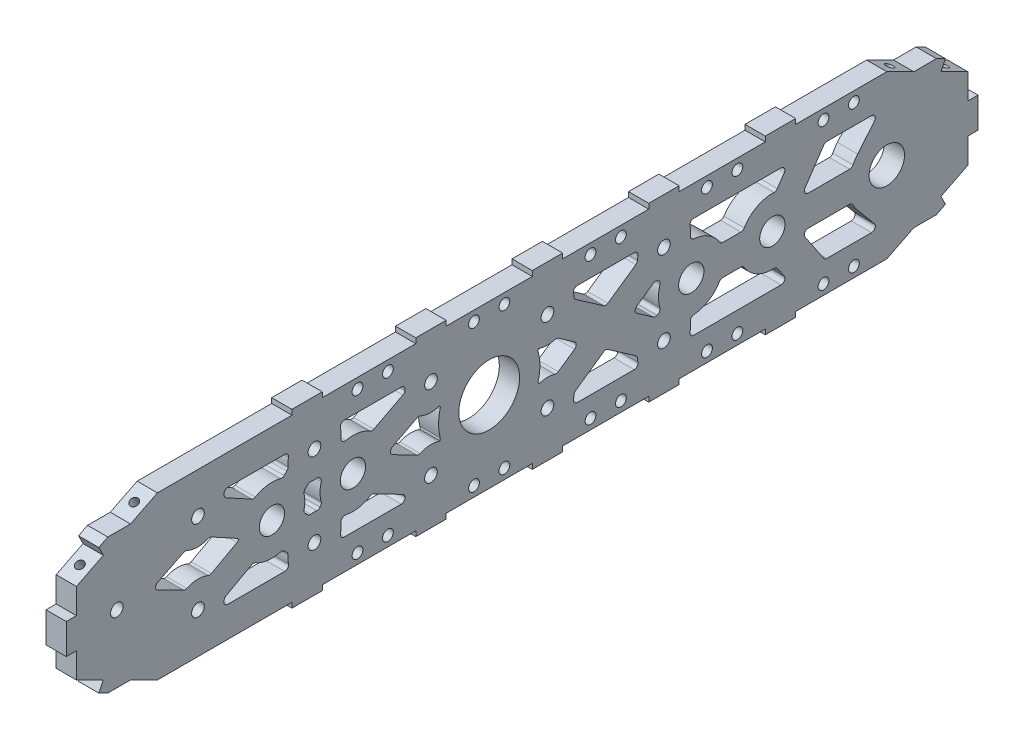
SolidWorks part; units mm, degrees
material "6061-T6 (SS)"
ref_plane "Front Plane" through (0, 0, 0) normal (0, 0, 1) x (1, 0, 0)
ref_plane "Top Plane" through (0, 0, 0) normal (0, 1, 0) x (1, 0, 0)
ref_plane "Right Plane" through (0, 0, 0) normal (1, 0, 0) x (0, 0, -1)
sketch "Sketch1" plane through (0, 0, 0) normal (1, 0, 0) x (0, 0, -1)
  line L0 (-160.655, 50.8) -> (93.345, 50.8)
  line L1 (93.345, 50.8) -> (93.345, -50.8)
  line L2 (93.345, -50.8) -> (-160.655, -50.8)
  line L3 (93.345, 0) -> (55.245, 50.8)
  line L4 (93.345, 0) -> (55.245, -50.8)
  circle A0 centre (0, 0) radius 38.1
  circle A1 centre (0, 0) radius 7.9375
  circle A2 centre (-38.1, 0) radius 7.9375
  circle A3 centre (-88.9, 0) radius 7.9375
  circle A4 centre (-88.9, 0) radius 39.751
  circle A5 centre (-38.1, 0) radius 25.4
  circle A6 centre (-160.655, 0) radius 11.1125
  circle A7 centre (-88.9, 0) radius 23.368
  circle A8 centre (-160.655, 0) radius 33.655
  circle A9 centre (-160.655, 0) radius 76.2
  circle A10 centre (-160.655, 0) radius 50.8
  dimension "D1" = 38.1
  dimension "D3" = 71.755
  dimension "D4" = 15.875
  dimension "D5" = 101.6
  dimension "D9" = 50.8
  dimension "D10" = 67.31
  dimension "D11" = 79.502
  dimension "D12" = 46.736
  dimension "D2" = 50.8
  dimension "D6" = 254
  dimension "D7" = 38.1
  dimension "D8" = 38.1
extrude "Boss-Extrude1" add sketch "Sketch1" along normal blind 12.7 contours A5 A0 A1 | A0 A5 | A10 A7 A9 A3 | A10 A7 A9 A4 | A7 A10 A4 | A7 A10 | A10 A4 A9 A7 | A9 A4 A5 A7 | A10 L2 A9 A4 | A4 A10 A8 | A8 A6 | A10 A4 A9 L0 | A9 A4 A5 A0 L2 L4 L3 L0 | A9 A3 A7 | A4 A5 | A0 A5 A4 A2 | A4 A8 | A6 | A1 region at (0, 24.069, -72.5203) region at (0, 42.9334, 118.4345) region at (0, 43.3242, 136.8815) region at (0, 26.7507, 103.5231) region at (0, 35.0406, 72.108) region at (0, -42.9334, 118.4345) region at (0, 0, 119.1262) region at (0, 24.4524, 42.4444) region at (0, 0, 55.9937) region at (0, 0, 97.9886) region at (0, 0, 76.9553) region at (0, -26.7507, 103.5231) region at (0, 0, 127.8393) region at (0, 0, 129.5966) region at (0, 0, 110.9718) region at (0, 0, 24.8917) region at (0, 34.9598, -12.3602) region at (0, 0, 0) region at (0, 0, 160.655)
hole_wizard "3/8-16 Tapped Hole1" positions "Sketch8" profile "Sketch7" tap size "3/8-16" standard "ANSI Inch"
sketch "Sketch8" plane through (12.7, 0, 0) normal (1, 0, 0) x (0, 0, -1)
  line L0 (10.795, 25.4) -> (-62.23, 25.4) construction
  line L1 (-62.23, 25.4) -> (-135.255, 25.4) construction
  line L2 (-135.255, 25.4) -> (-135.255, -25.4) construction
  line L3 (-135.255, -25.4) -> (-62.23, -25.4) construction
  line L4 (-62.23, -25.4) -> (10.795, -25.4) construction
  line L5 (10.795, -25.4) -> (10.795, 25.4) construction
  line L7 (-62.23, 25.4) -> (-62.23, -25.4) construction
  line L9 (93.345, 0) -> (61.595, 0) construction
  line L10 (61.595, 0) -> (-186.055, 0) construction
  line L11 (-186.055, 0) -> (-211.455, 0) construction
  line L16 (-160.655, 50.8) -> (55.245, 50.8) construction
  line L17 (55.245, -50.8) -> (-160.655, -50.8) construction
  arc A0 (-160.655, 50.8) -> (-160.655, -50.8) centre (-160.655, 0) ccw construction
  circle A1 centre (61.595, 0) radius 25.4
  circle A2 centre (10.795, 25.4) radius 25.4
  circle A3 centre (-62.23, 25.4) radius 25.4
  circle A4 centre (-135.255, 25.4) radius 25.4
  circle A5 centre (-186.055, 0) radius 25.4
  point P0 (61.595, 0)
  point P6 (-62.23, -25.4)
  point P8 (-135.255, -25.4)
  point P10 (-62.23, 25.4)
  point P12 (-135.255, 25.4)
  point P14 (-186.055, 0)
  dimension "D5" = 50.8
  dimension "D1" = 25.4
  dimension "D2" = 31.75
  dimension "D3" = 25.4
  dimension "D4" = 25.4
  dimension "D6" = 50.8
sketch "Sketch7" plane through (12.7, 0, -61.595) normal (0, 1, 0) x (0, 0, -1)
  line L0 (0, 0) -> (0, 26.2607)
  line L1 (0, 26.2607) -> (3.9687, 23.876)
  line L2 (3.9687, 23.876) -> (3.9687, 0)
  line L5 (3.9687, 0) -> (0, 0)
  line L10 (0, 26.2607) -> (-3.9688, 23.876) construction
  line L11 (0, -6.35) -> (0, 107.95) construction
  dimension "Tap Drill Dia." = 7.9375
  dimension "Tap Drill Depth" = 23.876
  dimension "Drill Angle" = 118
sketch "Sketch10" plane through (12.7, 0, 0) normal (1, 0, 0) x (0, 0, -1)
  line L0 (-211.455, 25.4) -> (-160.655, 50.8)
  line L1 (-211.455, 25.4) -> (-160.655, 50.8) construction
  line L2 (-160.655, 50.8) -> (-211.455, 50.8)
  line L3 (-211.455, 50.8) -> (-211.455, 25.4)
  line L4 (-211.455, -25.4) -> (-160.655, -50.8)
  line L5 (-160.655, -50.8) -> (-211.455, -50.8)
  line L6 (-211.455, -50.8) -> (-211.455, -25.4)
  arc A0 (-160.655, 50.8) -> (-160.655, -50.8) centre (-160.655, 0) ccw construction
extrude "Cut-Extrude3" cut sketch "Sketch10" against normal through all
sketch "Sketch11" plane through (12.7, 0, 0) normal (1, 0, 0) x (0, 0, -1)
  line L0 (-201.295, 30.48) -> (-211.455, 25.4)
  line L1 (-211.455, 25.4) -> (-211.455, -25.4)
  line L2 (-211.455, -25.4) -> (-201.295, -30.48)
  line L3 (-201.295, -30.48) -> (-201.295, 30.48)
extrude "Boss-Extrude2" add sketch "Sketch11" against normal blind 12.7
sketch "Sketch12" plane through (0, 0, 0) normal (-1, 0, 0) x (0, 0, 1)
  line L0 (-67.945, 33.8667) -> (-67.945, -33.8667)
  line L1 (-93.345, 0) -> (-55.245, 50.8) construction
  line L3 (-93.345, 0) -> (-55.245, -50.8) construction
  line L4 (-67.945, -33.8667) -> (-93.345, 0)
  line L5 (-93.345, 0) -> (-67.945, 33.8667)
  dimension "D1" = 25.4
extrude "Cut-Extrude4" cut sketch "Sketch12" against normal through all
mirror "Mirror1" about plane through (12.7, 33.8667, -67.945) normal (0, 0, 1) of "Boss-Extrude1", "Cut-Extrude3", "Boss-Extrude2"
sketch "Sketch13" plane through (12.7, 0, 0) normal (1, 0, 0) x (0, 0, -1)
  line L1 (55.245, 50.8) -> (80.645, 50.8)
  line L2 (55.245, 50.8) -> (55.245, -50.8)
  line L3 (55.245, -50.8) -> (80.645, -50.8)
  line L4 (80.645, 50.8) -> (80.645, -50.8)
extrude "Boss-Extrude3" add sketch "Sketch13" against normal up to surface (12.7 mm away) up to face at (0, 0, -67.945)
sketch "Sketch14" plane through (0, 0, 0) normal (-1, 0, 0) x (0, 0, 1)
  circle A0 centre (-296.545, 0) radius 11.1125
extrude "Cut-Extrude5" cut sketch "Sketch14" against normal through all
hole_wizard "3/8-16 Tapped Hole2" positions "Sketch16" profile "Sketch15" tap size "3/8-16" standard "ANSI Inch"
sketch "Sketch16" plane through (12.7, 0, 0) normal (1, 0, 0) x (0, 0, -1)
  line L0 (-62.23, 25.4) -> (10.795, 25.4) construction
  line L1 (10.795, 25.4) -> (83.82, 25.4) construction
  line L2 (83.82, 25.4) -> (156.845, 25.4) construction
  line L3 (156.845, 25.4) -> (156.845, -25.4) construction
  line L4 (156.845, -25.4) -> (83.82, -25.4) construction
  line L5 (83.82, -25.4) -> (10.795, -25.4) construction
  line L6 (10.795, -25.4) -> (-62.23, -25.4) construction
  line L7 (-62.23, -25.4) -> (-135.255, -25.4) construction
  point P0 (10.795, 25.4)
  point P2 (83.82, 25.4)
  point P4 (156.845, 25.4)
  point P6 (10.795, -25.4)
  point P8 (83.82, -25.4)
  point P10 (156.845, -25.4)
sketch "Sketch15" plane through (12.7, 25.4, -10.795) normal (0, 1, 0) x (0, 0, -1)
  line L0 (0, 0) -> (0, 26.2607)
  line L1 (0, 26.2607) -> (3.9687, 23.876)
  line L2 (3.9687, 23.876) -> (3.9687, 0)
  line L5 (3.9687, 0) -> (0, 0)
  line L10 (0, 26.2607) -> (-3.9687, 23.876) construction
  line L11 (0, -6.35) -> (0, 107.95) construction
  dimension "Tap Drill Dia." = 7.9375
  dimension "Tap Drill Depth" = 23.876
  dimension "Drill Angle" = 118
sketch "Sketch17" plane through (12.7, 0, 0) normal (1, 0, 0) x (0, 0, -1)
  line L0 (10.795, 25.4) -> (83.82, -25.4) construction
  line L1 (83.82, -25.4) -> (83.82, 25.4) construction
  line L2 (83.82, 25.4) -> (10.795, -25.4) construction
  line L3 (10.795, -25.4) -> (10.795, 25.4) construction
  circle A0 centre (47.3075, 0) radius 19.05
extrude "Cut-Extrude6" cut sketch "Sketch17" against normal through all
hole_wizard "1/4 Clearance Hole1" positions "Sketch20" profile "Sketch19" hole size "1/4" standard "ANSI Inch" end condition through all
sketch "Sketch20" plane through (12.7, 0, 0) normal (1, 0, 0) x (0, 0, -1)
  line L1 (-62.23, 25.4) -> (10.795, 25.4) construction
  line L2 (10.795, 25.4) -> (83.82, 25.4) construction
  line L3 (83.82, 25.4) -> (156.845, 25.4) construction
  line L4 (156.845, 25.4) -> (229.87, 25.4) construction
  line L5 (229.87, 25.4) -> (302.895, 25.4) construction
  line L9 (-160.655, 50.8) -> (296.545, 50.8) construction
  line L11 (-25.7175, 25.4) -> (-25.7175, 50.8) construction
  line L13 (47.3075, 25.4) -> (47.3075, 50.8) construction
  line L15 (120.3325, 25.4) -> (120.3325, 50.8) construction
  line L17 (193.3575, 25.4) -> (193.3575, 50.8) construction
  line L19 (266.3825, 25.4) -> (266.3825, 50.8) construction
  line L27 (-35.2425, 44.45) -> (-25.7175, 44.45) construction
  line L28 (-25.7175, 44.45) -> (-16.1925, 44.45) construction
  line L29 (-16.1925, 44.45) -> (37.7825, 44.45) construction
  line L30 (37.7825, 44.45) -> (47.3075, 44.45) construction
  line L31 (47.3075, 44.45) -> (56.8325, 44.45) construction
  line L32 (56.8325, 44.45) -> (110.8075, 44.45) construction
  line L33 (110.8075, 44.45) -> (120.3325, 44.45) construction
  line L34 (120.3325, 44.45) -> (129.8575, 44.45) construction
  line L35 (129.8575, 44.45) -> (183.8325, 44.45) construction
  line L36 (183.8325, 44.45) -> (193.3575, 44.45) construction
  line L37 (193.3575, 44.45) -> (202.8825, 44.45) construction
  line L38 (202.8825, 44.45) -> (256.8575, 44.45) construction
  line L39 (256.8575, 44.45) -> (266.3825, 44.45) construction
  line L40 (266.3825, 44.45) -> (275.9075, 44.45) construction
  point P51 (-35.2425, 44.45)
  point P53 (-16.1925, 44.45)
  point P55 (37.7825, 44.45)
  point P57 (56.8325, 44.45)
  point P59 (110.8075, 44.45)
  point P61 (129.8575, 44.45)
  point P63 (183.8325, 44.45)
  point P65 (202.8825, 44.45)
  point P67 (256.8575, 44.45)
  point P69 (275.9075, 44.45)
  dimension "D1" = 9.525
  dimension "D2" = 6.35
sketch "Sketch19" plane through (12.7, 44.45, 35.2425) normal (0, 1, 0) x (0, 0, -1)
  line L0 (0, 0) -> (0, 12.7)
  line L1 (0, 12.7) -> (3.3782, 12.7)
  line L2 (3.3782, 12.7) -> (3.3782, 0)
  line L5 (3.3782, 0) -> (0, 0)
  line L11 (0, -6.35) -> (0, 107.95) construction
  dimension "Thru Hole Dia." = 6.7564
  dimension "Thru Hole Depth" = 12.7
sketch "Sketch21" plane through (12.7, 0, 0) normal (1, 0, 0) x (0, 0, -1)
  line L0 (-98.425, 44.45) -> (-35.2425, 44.45) construction
  line L1 (-35.2425, 44.45) -> (-16.1925, 44.45) construction
  line L2 (-16.1925, 44.45) -> (37.7825, 44.45) construction
  line L3 (37.7825, 44.45) -> (56.8325, 44.45) construction
  line L4 (56.8325, 44.45) -> (110.8075, 44.45) construction
  line L5 (110.8075, 44.45) -> (129.8575, 44.45) construction
  line L6 (129.8575, 44.45) -> (183.8325, 44.45) construction
  line L7 (183.8325, 44.45) -> (202.8825, 44.45) construction
  line L8 (202.8825, 44.45) -> (256.8575, 44.45) construction
  line L9 (-66.8337, 44.45) -> (-66.8337, 50.8) construction
  line L10 (-160.655, 50.8) -> (296.545, 50.8) construction
  line L12 (10.795, 44.45) -> (10.795, 50.8) construction
  line L13 (-76.3587, 50.8) -> (-57.3087, 50.8)
  line L14 (83.82, 44.45) -> (83.82, 50.8) construction
  line L15 (-76.3587, 50.8) -> (-76.3587, 53.975)
  line L16 (156.845, 44.45) -> (156.845, 50.8) construction
  line L17 (-76.3587, 53.975) -> (-57.3087, 53.975)
  line L18 (229.87, 44.45) -> (229.87, 50.8) construction
  line L19 (-57.3087, 50.8) -> (-57.3087, 53.975)
  line L20 (1.27, 50.8) -> (20.32, 50.8)
  line L21 (1.27, 50.8) -> (1.27, 53.975)
  line L22 (1.27, 53.975) -> (20.32, 53.975)
  line L23 (20.32, 50.8) -> (20.32, 53.975)
  line L24 (74.295, 50.8) -> (93.345, 50.8)
  line L25 (74.295, 50.8) -> (74.295, 53.975)
  line L26 (74.295, 53.975) -> (93.345, 53.975)
  line L27 (93.345, 50.8) -> (93.345, 53.975)
  line L28 (147.32, 50.8) -> (166.37, 50.8)
  line L29 (147.32, 50.8) -> (147.32, 53.975)
  line L30 (147.32, 53.975) -> (166.37, 53.975)
  line L31 (166.37, 50.8) -> (166.37, 53.975)
  line L32 (220.345, 50.8) -> (239.395, 50.8)
  line L33 (220.345, 50.8) -> (220.345, 53.975)
  line L34 (220.345, 53.975) -> (239.395, 53.975)
  line L35 (239.395, 50.8) -> (239.395, 53.975)
  dimension "D1" = 19.05
  dimension "D2" = 3.175
  dimension "D3" = 98.425
extrude "Boss-Extrude4" add sketch "Sketch21" against normal up to surface (12.7 mm away) up to face at (0, 44.45, 31.8643)
mirror "Mirror2" about plane through (0, 0, 0) normal (0, 1, 0) of "Boss-Extrude4", "1/4 Clearance Hole1"
sketch "Sketch22" plane through (12.7, 0, 0) normal (1, 0, 0) x (0, 0, -1)
  line L0 (347.345, 25.4) -> (347.345, -25.4) construction
  line L1 (347.345, 9.525) -> (353.695, 9.525)
  line L2 (347.345, 9.525) -> (347.345, -9.525)
  line L3 (347.345, -9.525) -> (353.695, -9.525)
  line L4 (353.695, 9.525) -> (353.695, -9.525)
  line L5 (-211.455, 25.4) -> (-211.455, -25.4) construction
  line L6 (-211.455, 9.525) -> (-217.805, 9.525)
  line L7 (-211.455, 9.525) -> (-211.455, -9.525)
  line L8 (-211.455, -9.525) -> (-217.805, -9.525)
  line L9 (-217.805, 9.525) -> (-217.805, -9.525)
  line L10 (-194.5744, 33.8403) -> (-197.4142, 39.5199)
  line L11 (-211.455, 25.4) -> (-160.655, 50.8) construction
  line L12 (-197.4142, 39.5199) -> (-180.3754, 48.0393)
  line L13 (-180.3754, 48.0393) -> (-177.5356, 42.3597)
  line L14 (-177.5356, 42.3597) -> (-194.5744, 33.8403)
  line L15 (-194.5744, -33.8403) -> (-197.4142, -39.5199)
  line L16 (-160.655, -50.8) -> (-211.455, -25.4) construction
  line L17 (-197.4142, -39.5199) -> (-180.3754, -48.0393)
  line L18 (-180.3754, -48.0393) -> (-177.5356, -42.3597)
  line L19 (-177.5356, -42.3597) -> (-194.5744, -33.8403)
  line L20 (313.4256, -42.3597) -> (316.2654, -48.0393)
  line L21 (296.545, -50.8) -> (347.345, -25.4) construction
  line L22 (316.2654, -48.0393) -> (333.3042, -39.5199)
  line L23 (333.3042, -39.5199) -> (330.4644, -33.8403)
  line L24 (330.4644, -33.8403) -> (313.4256, -42.3597)
  line L25 (330.4644, 33.8403) -> (333.3042, 39.5199)
  line L26 (347.345, 25.4) -> (296.545, 50.8) construction
  line L27 (333.3042, 39.5199) -> (316.2654, 48.0393)
  line L28 (316.2654, 48.0393) -> (313.4256, 42.3597)
  line L29 (313.4256, 42.3597) -> (330.4644, 33.8403)
  line L30 (-177.5356, 42.3597) -> (-191.7346, 42.3597)
  line L31 (-177.5356, -42.3597) -> (-191.7346, -42.3597)
  line L32 (313.4256, -42.3597) -> (327.6246, -42.3597)
  line L33 (313.4256, 42.3597) -> (327.6246, 42.3597)
  point P34 (-186.055, 38.1)
  point P37 (-211.455, 0)
  point P38 (-186.055, -38.1)
  point P39 (321.945, -38.1)
  point P40 (347.345, 0)
  point P41 (321.945, 38.1)
  dimension "D1" = 6.35
  dimension "D2" = 19.05
extrude "Boss-Extrude5" add sketch "Sketch22" against normal up to surface (12.7 mm away) contours L14 L30 L12 L10 | L6 L9 L8 L7 | L31 L19 L15 L17 | L24 L32 L22 L23 | L4 L1 L2 L3 | L33 L29 L25 L27 region at (12.7, 0, -350.52) region at (12.7, 0, 214.63) region at (12.7, 39.2833, 189.6048) region at (12.7, -39.2833, 189.6048) region at (12.7, -39.2833, -325.4948) region at (12.7, 39.2833, -325.4948) up to face at (0, -44.45, 31.8643)
hole_wizard "1/4-20 Tapped Hole1" positions "Sketch24" profile "Sketch23" tap size "1/4-20" standard "ANSI Inch"
sketch "Sketch24" plane through (0, -104.902, 52.451) normal (0, -0.8944, 0.4472) x (-1, 0, 0)
  point P0 (-6.35, -130.1469)
  point P2 (-6.35, -168.2469)
sketch "Sketch23" plane through (6.35, -46.6985, 168.8579) normal (1, 0, 0) x (0, -0.4472, -0.8944)
  line L0 (0, 0) -> (0, 24.3938)
  line L1 (0, 24.3938) -> (2.5527, 22.86)
  line L2 (2.5527, 22.86) -> (2.5527, 0)
  line L5 (2.5527, 0) -> (0, 0)
  line L10 (0, 24.3938) -> (-2.5527, 22.86) construction
  line L11 (0, -6.35) -> (0, 107.95) construction
  dimension "Tap Drill Dia." = 5.1054
  dimension "Tap Drill Depth" = 22.86
  dimension "Drill Angle" = 118
hole_wizard "1/4-20 Tapped Hole2" positions "Sketch26" profile "Sketch25" tap size "1/4-20" standard "ANSI Inch"
sketch "Sketch26" plane through (0, 104.902, 52.451) normal (0, 0.8944, 0.4472) x (1, 0, 0)
  point P0 (6.35, -130.1469)
  point P2 (6.35, -168.2469)
sketch "Sketch25" plane through (6.35, 46.6985, 168.8579) normal (1, 0, 0) x (0, -0.4472, 0.8944)
  line L0 (0, 0) -> (0, 24.3938)
  line L1 (0, 24.3938) -> (2.5527, 22.86)
  line L2 (2.5527, 22.86) -> (2.5527, 0)
  line L5 (2.5527, 0) -> (0, 0)
  line L10 (0, 24.3938) -> (-2.5527, 22.86) construction
  line L11 (0, -6.35) -> (0, 107.95) construction
  dimension "Tap Drill Dia." = 5.1054
  dimension "Tap Drill Depth" = 22.86
  dimension "Drill Angle" = 118
hole_wizard "1/4-20 Tapped Hole3" positions "Sketch28" profile "Sketch27" tap size "1/4-20" standard "ANSI Inch"
sketch "Sketch28" plane through (0, -159.258, -79.629) normal (0, -0.8944, -0.4472) x (-1, 0, 0)
  point P0 (-6.35, 289.7906)
  point P2 (-6.35, 251.6906)
sketch "Sketch27" plane through (6.35, -29.6597, -338.8256) normal (1, 0, 0) x (0, 0.4472, -0.8944)
  line L0 (0, 0) -> (0, 24.3938)
  line L1 (0, 24.3938) -> (2.5527, 22.86)
  line L2 (2.5527, 22.86) -> (2.5527, 0)
  line L5 (2.5527, 0) -> (0, 0)
  line L10 (0, 24.3938) -> (-2.5527, 22.86) construction
  line L11 (0, -6.35) -> (0, 107.95) construction
  dimension "Tap Drill Dia." = 5.1054
  dimension "Tap Drill Depth" = 22.86
  dimension "Drill Angle" = 118
hole_wizard "1/4-20 Tapped Hole4" positions "Sketch30" profile "Sketch29" tap size "1/4-20" standard "ANSI Inch"
sketch "Sketch30" plane through (0, 159.258, -79.629) normal (0, 0.8944, -0.4472) x (1, 0, 0)
  point P0 (6.35, 251.6906)
  point P2 (6.35, 289.7906)
sketch "Sketch29" plane through (6.35, 46.6985, -304.7479) normal (1, 0, 0) x (0, 0.4472, 0.8944)
  line L0 (0, 0) -> (0, 24.3938)
  line L1 (0, 24.3938) -> (2.5527, 22.86)
  line L2 (2.5527, 22.86) -> (2.5527, 0)
  line L5 (2.5527, 0) -> (0, 0)
  line L10 (0, 24.3938) -> (-2.5527, 22.86) construction
  line L11 (0, -6.35) -> (0, 107.95) construction
  dimension "Tap Drill Dia." = 5.1054
  dimension "Tap Drill Depth" = 22.86
  dimension "Drill Angle" = 118
sketch "Sketch31" plane through (12.7, 0, 0) normal (1, 0, 0) x (0, 0, -1)
  line L0 (-139.8321, 17.0468) -> (-93.4771, -8.3532)
  line L1 (-93.4771, 8.3532) -> (-139.8321, -17.0468)
  line L2 (-82.331, -6.8974) -> (-62.5671, 11.9254)
  line L3 (-62.5671, 11.9254) -> (-45.0056, -6.5603)
  line L4 (-45.0056, 6.5603) -> (-62.5671, -11.9254)
  line L5 (-62.5671, -11.9254) -> (-82.331, 6.8974)
  line L6 (-33.7091, -8.4525) -> (10.0794, 14.2947)
  line L7 (10.0794, 14.2947) -> (41.8681, -7.8191)
  line L8 (41.8681, 7.8191) -> (10.0794, -14.2947)
  line L9 (10.0794, -14.2947) -> (-33.7091, 8.4525)
  line L10 (52.7469, -7.8191) -> (89.2594, 17.5809)
  line L11 (89.2594, -17.5809) -> (52.7469, 7.8191)
  line L12 (148.9502, 20.071) -> (166.0952, -5.329)
  line L13 (166.0952, 5.329) -> (148.9502, -20.071)
  line L14 (173.99, -9.525) -> (224.79, -9.525)
  line L15 (224.79, -9.525) -> (296.545, -9.525)
  line L16 (-130.6779, 33.7532) -> (-84.3229, 8.3532)
  line L17 (-84.3229, -8.3532) -> (-130.6779, -33.7532)
  line L18 (-95.469, 6.8974) -> (-61.8929, 38.8746)
  line L19 (-61.8929, 38.8746) -> (-31.1944, 6.5603)
  line L20 (-31.1944, -6.5603) -> (-61.8929, -38.8746)
  line L21 (-61.8929, -38.8746) -> (-95.469, -6.8974)
  line L22 (-42.4909, 8.4525) -> (11.5106, 36.5053)
  line L23 (11.5106, 36.5053) -> (52.7469, 7.8191)
  line L24 (52.7469, -7.8191) -> (11.5106, -36.5053)
  line L25 (11.5106, -36.5053) -> (-42.4909, -8.4525)
  line L26 (41.8681, 7.8191) -> (78.3806, 33.2191)
  line L27 (78.3806, -33.2191) -> (41.8681, -7.8191)
  line L28 (164.7398, 30.729) -> (181.8848, 5.329)
  line L29 (181.8848, -5.329) -> (164.7398, -30.729)
  line L30 (173.99, 9.525) -> (224.79, 9.525)
  line L31 (224.79, 9.525) -> (296.545, 9.525)
  line L32 (292.0479, 31.75) -> (278.2744, 15.2715)
  line L33 (292.0479, -31.75) -> (278.2744, -15.2715)
  line L34 (-186.055, 0) -> (-135.255, 25.4) construction
  line L35 (-186.055, 0) -> (-135.255, -25.4) construction
  line L36 (-164.7565, 0) -> (-130.9953, -16.8806)
  line L37 (-164.7565, 0) -> (-130.9953, 16.8806)
  line L38 (-207.3535, 0) -> (-139.5147, -33.9194)
  line L39 (-207.3535, 0) -> (-139.5147, 33.9194)
  line L40 (83.82, 25.4) -> (156.845, -25.4) construction
  line L41 (83.82, -25.4) -> (156.845, 25.4) construction
  line L42 (224.79, 0) -> (246.2213, 31.75) construction
  line L43 (254.116, -26.421) -> (236.2818, 0)
  line L44 (246.2213, -31.75) -> (224.79, 0) construction
  line L45 (236.2818, 0) -> (254.116, 26.421)
  line L46 (238.3265, -37.079) -> (213.2982, 0)
  line L47 (213.2982, 0) -> (238.3265, 37.079)
  line L48 (254.116, 26.421) -> (257.7131, 31.75)
  line L49 (78.3806, 17.5809) -> (151.4056, -33.2191)
  line L50 (257.7131, -31.75) -> (254.116, -26.421)
  line L51 (89.2594, -33.2191) -> (162.2844, 17.5809)
  line L52 (89.2594, 33.2191) -> (162.2844, -17.5809)
  line L53 (78.3806, -17.5809) -> (151.4056, 33.2191)
  line L72 (-135.255, 21.4312) -> (-135.255, 8.7312) construction
  line L73 (-135.255, 25.4) -> (-88.9, 0) construction
  line L74 (-88.9, -7.9375) -> (-88.9, -20.6375) construction
  line L75 (-88.9, 0) -> (-62.23, 25.4) construction
  line L76 (47.3075, -19.05) -> (47.3075, -31.75) construction
  line L77 (-62.23, 25.4) -> (-38.1, 0) construction
  line L78 (296.545, -11.1125) -> (296.545, -23.8125) construction
  line L79 (-38.1, 0) -> (10.795, 25.4) construction
  line L80 (10.795, 25.4) -> (47.3075, 0) construction
  line L81 (47.3075, 0) -> (83.82, 25.4) construction
  line L82 (156.845, 25.4) -> (173.99, 0) construction
  line L83 (173.99, 0) -> (224.79, 0) construction
  line L84 (224.79, 0) -> (296.545, 0) construction
  line L85 (173.99, 0) -> (156.845, -25.4) construction
  line L86 (83.82, -25.4) -> (47.3075, 0) construction
  line L87 (47.3075, 0) -> (10.795, -25.4) construction
  line L88 (10.795, -25.4) -> (-38.1, 0) construction
  line L89 (-38.1, 0) -> (-62.23, -25.4) construction
  line L90 (-62.23, -25.4) -> (-88.9, 0) construction
  line L91 (-88.9, 0) -> (-135.255, -25.4) construction
  line L144 (328.295, 13.6265) -> (292.0479, 31.75)
  line L145 (292.0479, 31.75) -> (-156.1579, 31.75)
  line L146 (-156.1579, 31.75) -> (-192.405, 13.6265)
  line L147 (-192.405, 13.6265) -> (-192.405, -13.6265)
  line L148 (-192.405, -13.6265) -> (-156.1579, -31.75)
  line L149 (-156.1579, -31.75) -> (292.0479, -31.75)
  line L150 (292.0479, -31.75) -> (328.295, -13.6265)
  line L151 (328.295, -13.6265) -> (328.295, 13.6265)
  line L152 (328.295, 13.6265) -> (292.0479, 31.75)
  line L153 (292.0479, 31.75) -> (-156.1579, 31.75)
  line L154 (-156.1579, 31.75) -> (-192.405, 13.6265)
  line L155 (-192.405, 13.6265) -> (-192.405, -13.6265)
  line L156 (-192.405, -13.6265) -> (-156.1579, -31.75)
  line L157 (-156.1579, -31.75) -> (292.0479, -31.75)
  line L158 (292.0479, -31.75) -> (328.295, -13.6265)
  line L159 (328.295, -13.6265) -> (328.295, 13.6265)
  circle A0 centre (-186.055, 0) radius 16.6687
  circle A1 centre (-135.255, 25.4) radius 16.6687
  circle A2 centre (-135.255, -25.4) radius 16.6687
  circle A3 centre (-62.23, -25.4) radius 16.6687
  circle A4 centre (10.795, -25.4) radius 16.6687
  circle A5 centre (83.82, -25.4) radius 16.6687
  circle A6 centre (156.845, -25.4) radius 16.6687
  circle A7 centre (156.845, 25.4) radius 16.6687
  circle A8 centre (83.82, 25.4) radius 16.6687
  circle A9 centre (10.795, 25.4) radius 16.6687
  circle A10 centre (-62.23, 25.4) radius 16.6687
  circle A11 centre (-38.1, 0) radius 20.6375
  circle A12 centre (-88.9, 0) radius 20.6375
  circle A13 centre (47.3075, 0) radius 31.75
  circle A14 centre (173.99, 0) radius 20.6375
  circle A15 centre (224.79, 0) radius 20.6375
  circle A16 centre (296.545, 0) radius 23.8125
  circle A17 centre (-135.255, 25.4) radius 3.9687 construction
  circle A18 centre (-88.9, 0) radius 7.9375 construction
  circle A19 centre (47.3075, 0) radius 19.05 construction
  circle A20 centre (296.545, 0) radius 11.1125 construction
  dimension "D2" = 12.7
  dimension "D3" = 9.525
  dimension "D5" = 9.525
  dimension "D7" = 9.525
  dimension "D9" = 9.525
  dimension "D1" = 19.05
  dimension "D4" = 9.525
  dimension "D6" = 9.525
  dimension "D8" = 9.525
  dimension "D10" = 9.525
extrude "Cut-Extrude7" cut sketch "Sketch31" against normal through all contours A12 L0 A1 L37 L36 A2 L1 | A12 L18 A10 L153 A1 L16 | A12 L17 A2 L157 A3 L21 | A12 L5 A3 L4 A11 L3 A10 L2 | A11 L22 A9 L153 A10 L19 | A11 L20 A3 L157 A4 L25 | A13 L7 A9 L6 L9 A4 L8 | A13 L11 A5 L53 L49 A8 L10 | A8 L52 L53 A7 L153 | A6 L49 L51 A5 L157 | A14 A7 L51 L52 A6 | A15 L14 A14 A6 L157 L46 | A15 L47 L153 A7 A14 L30 | A16 L32 L153 L48 L45 A15 L31 | A16 L15 A15 L43 L50 L157 L33 region at (12.7, 0, 136.4364) region at (12.7, 26.1565, 97.3681) region at (12.7, -26.1565, 97.3681) region at (12.7, 26.1294, 27.4599) region at (12.7, 0, 63.3173) region at (12.7, -26.1294, 27.4599) region at (12.7, 0, -3.1416) region at (12.7, 24.5838, -120.3325) region at (12.7, -24.5838, -120.3325) region at (12.7, 23.2725, -201.3051) region at (12.7, 0, -88.2455) region at (12.7, 0, -148.1475) region at (12.7, -23.2725, -201.3051) region at (12.7, 20.808, -266.6707) region at (12.7, -20.808, -266.6707)
fillet "Fillet1" radius 2.3813 86 edges at (6.35, -31.75, -292.0479) (6.35, -31.75, -257.7131) (6.35, -9.525, -274.7205) (6.35, 9.525, -274.7205) (6.35, 31.75, -292.0479) (6.35, 31.75, -257.7131) (6.35, -20.5035, -227.138) (6.35, -31.75, -234.7294) (6.35, -31.75, -172.2568) (6.35, -9.525, -192.2979) (6.35, -9.525, -206.4821) (6.35, -20.6037, -172.8088) (6.35, 9.525, -206.4821) (6.35, 9.525, -192.2979) (6.35, 20.6037, -172.8088) (6.35, 31.75, -234.7294) (6.35, 20.5035, -227.138) (6.35, 31.75, -172.2568) (6.35, -8.8009, -155.3232) (6.35, -9.7691, -151.055) (6.35, 9.7691, -151.055) (6.35, 8.8009, -155.3232) (6.35, 0, -137.0119) (6.35, -31.75, -141.4332) (6.35, -31.75, -99.2318) (6.35, -11.603, -120.3325) (6.35, -25.4074, -140.1763) (6.35, -25.4074, -100.4887) (6.35, 31.75, -141.4332) (6.35, 25.4074, -140.1763) (6.35, 11.603, -120.3325) (6.35, 25.4074, -100.4887) (6.35, 31.75, -99.2318) (6.35, 9.477, -77.6101) (6.35, 9.7691, -89.61) (6.35, 0, -103.6531) (6.35, -9.7691, -89.61) (6.35, -9.7691, -78.03) (6.35, -9.477, -77.6101) (6.35, 9.7691, -78.03) (6.35, -9.477, -17.0049) (6.35, -9.7691, -16.585) (6.35, -10.6415, -3.0469) (6.35, 10.6415, -3.0469) (6.35, 9.7691, -16.585) (6.35, 9.477, -17.0049) (6.35, 0, 17.4379) (6.35, -16.8923, 26.2444) (6.35, -27.5465, 5.735) (6.35, -31.75, 4.6168) (6.35, -22.0429, 45.9028) (6.35, -19.8336, 43.804) (6.35, -31.75, 46.8182) (6.35, 19.8336, 43.804) (6.35, 31.75, 46.8182) (6.35, 31.75, 4.6168) (6.35, 27.5465, 5.735) (6.35, 16.8923, 26.2444) (6.35, 22.0429, 45.9028) (6.35, 5.7288, 69.0736) (6.35, 9.0686, 65.5667) (6.35, 8.9222, 59.7141) (6.35, 6.7129, 57.6152) (6.35, -6.7129, 57.6152) (6.35, -8.9222, 59.7141) (6.35, -9.0686, 65.5667) (6.35, -5.7288, 69.0736) (6.35, -19.5236, 82.2115) (6.35, -22.8635, 78.7046) (6.35, -31.75, 77.6418) (6.35, -31.75, 119.8432) (6.35, -17.1508, 100.3785) (6.35, -27.1798, 118.6815) (6.35, 17.1508, 100.3785) (6.35, 27.1798, 118.6815) (6.35, 31.75, 77.6418) (6.35, 22.8635, 78.7046) (6.35, 19.5236, 82.2115) (6.35, 31.75, 119.8432) (6.35, -0.4444, 109.5327) (6.35, -10.4735, 127.8357) (6.35, -10.763, 143.2304) (6.35, 10.763, 143.2304) (6.35, 10.4735, 127.8357) (6.35, 0.4444, 109.5327) (6.35, 0, 164.7565)
sketch "Sketch32" plane through (12.7, 0, 0) normal (1, 0, 0) x (0, 0, -1)
  line L0 (257.005, -30.701) -> (242.9276, -9.8455) construction
  line L1 (243.0979, -9.525) -> (273.2136, -9.525) construction
  line L2 (243.0979, 9.525) -> (273.2136, 9.525) construction
  line L3 (242.9276, 9.8455) -> (257.005, 30.701) construction
  line L4 (243.0979, -9.525) -> (273.2136, -9.525)
  line L5 (257.005, -30.701) -> (242.9276, -9.8455)
  line L6 (242.9276, 9.8455) -> (257.005, 30.701)
  line L7 (243.0979, 9.525) -> (273.2136, 9.525)
  circle A0 centre (247.1915, 11.9062) radius 2.3813
  circle A1 centre (247.1915, -11.9062) radius 2.3813
  arc A2 (242.9276, -9.8455) -> (243.0979, -9.525) centre (224.79, 0) ccw construction
  arc A3 (242.9276, -9.8455) -> (243.0979, -9.525) centre (224.79, 0) ccw
  arc A4 (243.0979, 9.525) -> (242.9276, 9.8455) centre (224.79, 0) ccw construction
  arc A5 (243.0979, 9.525) -> (242.9276, 9.8455) centre (224.79, 0) ccw
  dimension "D1" = 4.7625
extrude "Boss-Extrude6" add sketch "Sketch32" against normal up to surface (12.7 mm away) contours A5 L7 A0 L6 | A3 L5 A1 L4 region at (12.7, -10.4606, -244.4715) region at (12.7, 10.4606, -244.4715) up to face at (0, 19.7383, -267.3043)
